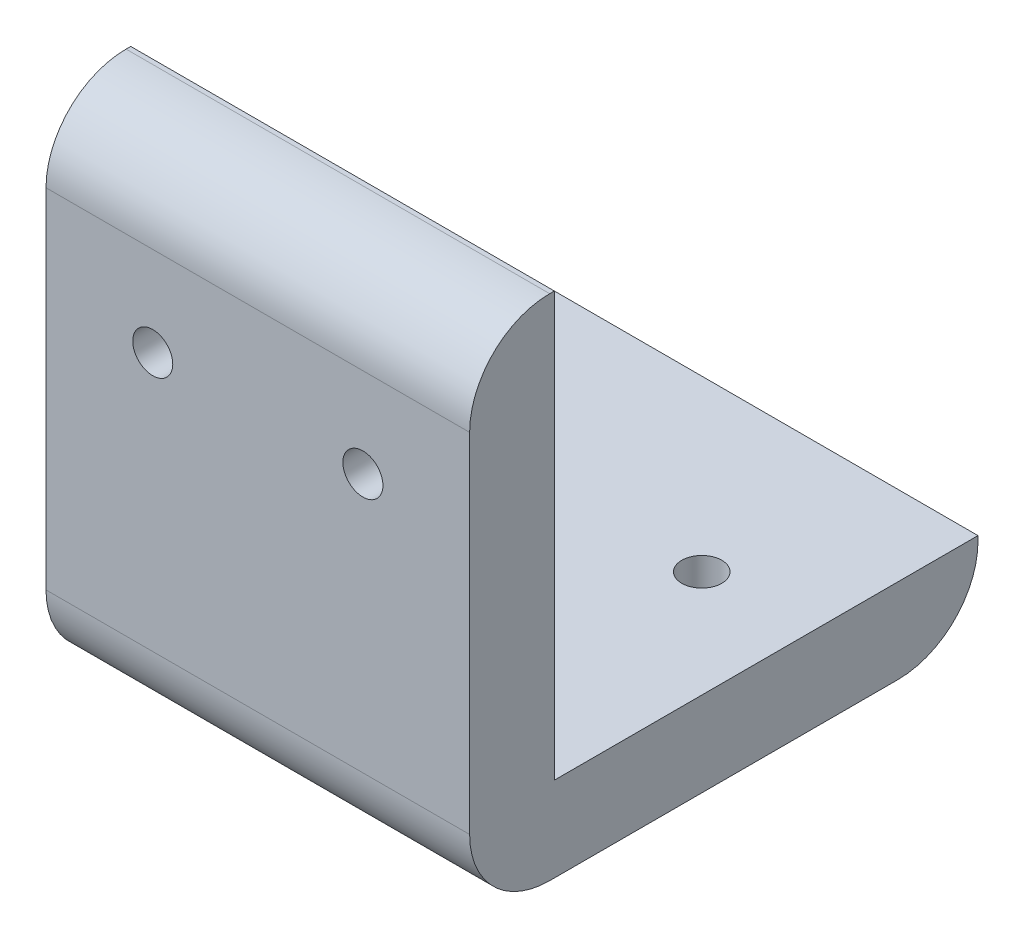
SolidWorks part; units mm, degrees
ref_plane "Front Plane" through (0, 0, 0) normal (0, 0, 1) x (1, 0, 0)
ref_plane "Top Plane" through (0, 0, 0) normal (0, 1, 0) x (1, 0, 0)
ref_plane "Right Plane" through (0, 0, 0) normal (1, 0, 0) x (0, 0, -1)
sketch "Sketch1" plane through (0, 0, 0) normal (1, 0, 0) x (0, 0, -1)
  line L0 (-6.35, 31.75) -> (-6.35, -6.35)
  line L1 (-6.35, -6.35) -> (31.75, -6.35)
  line L2 (31.75, -6.35) -> (31.75, 0)
  line L3 (31.75, 0) -> (0, 0)
  line L4 (0, 0) -> (0, 31.75)
  line L5 (0, 31.75) -> (-6.35, 31.75)
  point P5 (0, 0)
  dimension "D1" = 6.35
  dimension "D2" = 6.35
  dimension "D3" = 31.75
  dimension "D4" = 31.75
extrude "Boss-Extrude1" add sketch "Sketch1" along normal blind 31.75
fillet "Fillet1" radius 6 2 edges at (15.875, 31.75, 6.35) (15.875, -6.35, -31.75)
sketch "Sketch2" plane through (0, 0, 6.35) normal (0, 0, 1) x (1, 0, 0)
  line L0 (8, 19.05) -> (23.75, 19.05) construction
  line L1 (31.75, -6.35) -> (0, -6.35) construction
  line L2 (31.75, 25.75) -> (31.75, -6.35) construction
  circle A0 centre (8, 19.05) radius 1.5
  circle A1 centre (23.75, 19.05) radius 1.5
  point P4 (15.875, 19.05)
  point P7 (15.875, -6.35)
  point P8 (0, 0)
  dimension "D1" = 3
  dimension "D2" = 8
  dimension "D3" = 19.05
extrude "Cut-Extrude1" cut sketch "Sketch2" against normal through all
sketch "Sketch3" plane through (0, -6.35, 0) normal (0, -1, 0) x (1, 0, 0)
  line L0 (8, -19.05) -> (23.75, -19.05) construction
  line L1 (31.75, 6.35) -> (0, 6.35) construction
  line L3 (0, 6.35) -> (0, -25.75) construction
  circle A0 centre (8, -19.05) radius 1.5
  circle A1 centre (23.75, -19.05) radius 1.5
  point P4 (15.875, -19.05)
  point P5 (23.9681, -12.7)
  point P8 (0, 0)
  point P12 (0, 0)
  point P14 (8.6403, -11.22)
  point P18 (15.875, 6.35)
  dimension "D1" = 3
  dimension "D2" = 8
  dimension "D3" = 19.05
extrude "Cut-Extrude2" cut sketch "Sketch3" against normal through all
fillet "Fillet2" radius 6 1 edges at (15.875, -6.35, 6.35)
